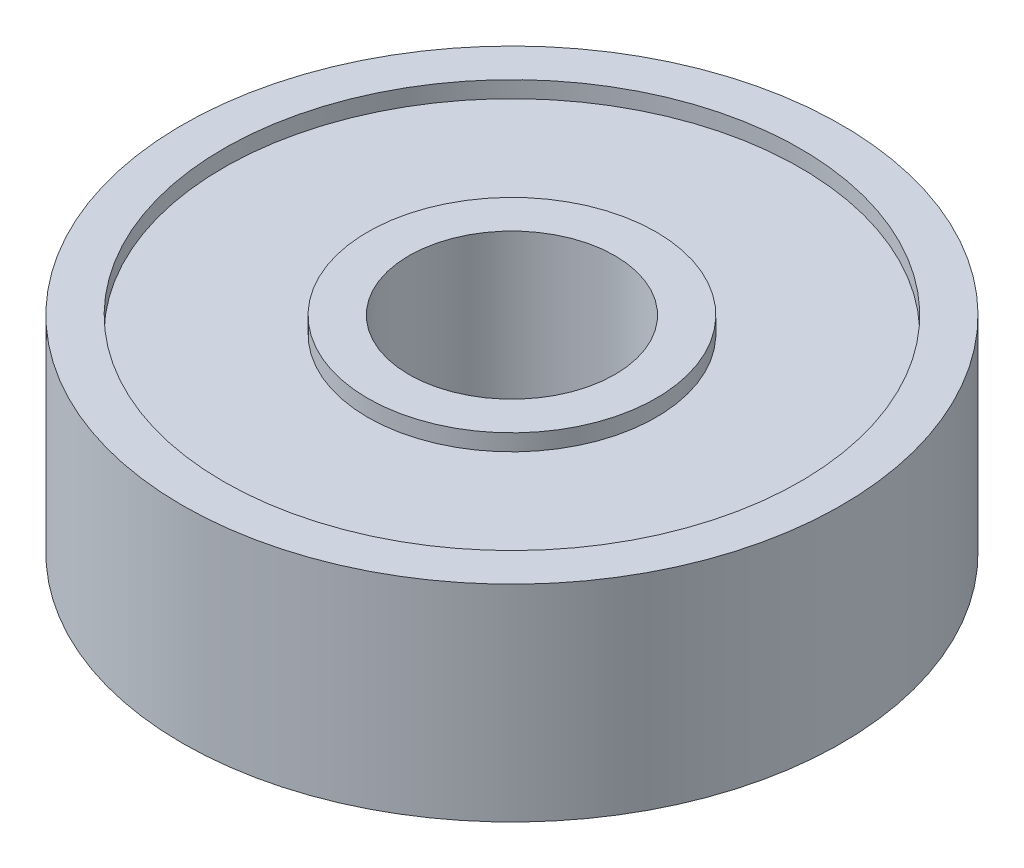
SolidWorks part; units mm, degrees
ref_plane "Front Plane" through (0, 0, 0) normal (0, 0, 1) x (1, 0, 0)
ref_plane "Top Plane" through (0, 0, 0) normal (0, 1, 0) x (1, 0, 0)
ref_plane "Right Plane" through (0, 0, 0) normal (1, 0, 0) x (0, 0, -1)
sketch "Sketch1" plane through (0, 0, 0) normal (0, 1, 0) x (1, 0, 0)
  circle A0 centre (0, 0) radius 8
  dimension "D1" = 16
extrude "Boss-Extrude1" add sketch "Sketch1" along normal blind 2.5 and the other way blind 2.5
sketch "Sketch2" plane through (0, 2.5, 0) normal (0, 1, 0) x (1, 0, 0)
  circle A0 centre (0, 0) radius 2.5
  dimension "D1" = 5
extrude "Cut-Extrude1" cut sketch "Sketch2" against normal through all
sketch "Sketch3" plane through (0, 2.5, 0) normal (0, 1, 0) x (1, 0, 0)
  circle A7 centre (0, 0) radius 3.5
  circle A8 centre (0, 0) radius 3.5
  circle A10 centre (0, 0) radius 7
  circle A11 centre (0, 0) radius 7
  dimension "D1" = 1
  dimension "D2" = 1
extrude "Cut-Extrude2" cut sketch "Sketch3" against normal blind 0.4
mirror "Mirror1" about plane through (0, 0, 0) normal (0, 1, 0) of "Cut-Extrude2"
